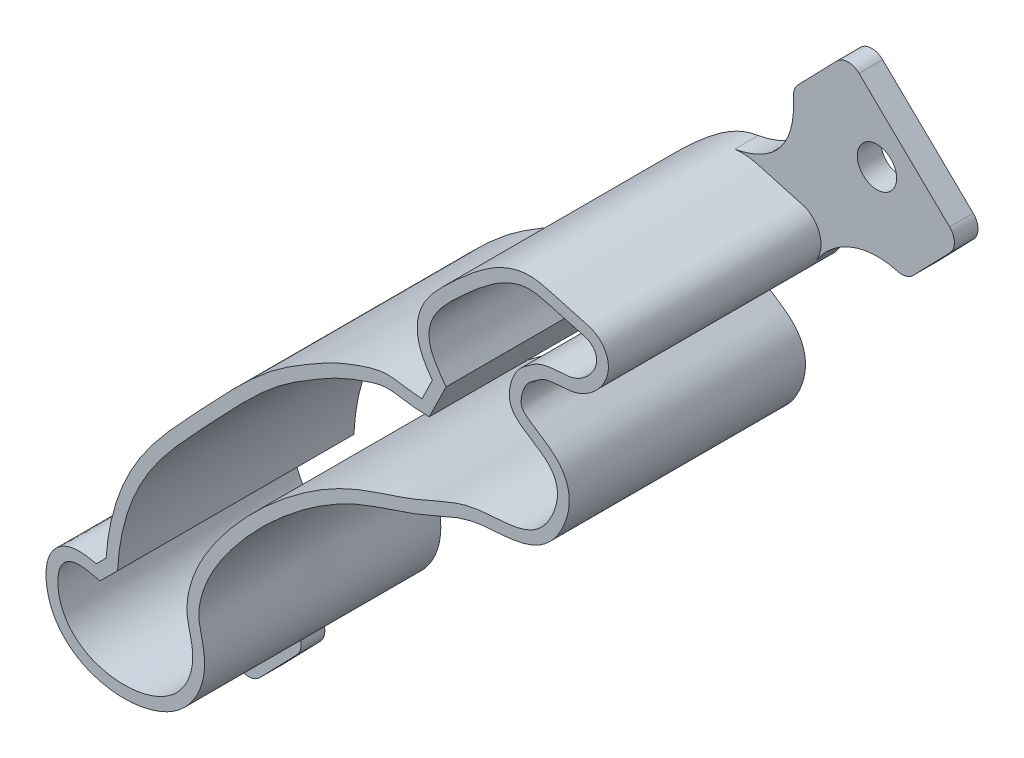
SolidWorks part; units mm, degrees
ref_plane "Ebene vorne" through (0, 0, 0) normal (0, 0, 1) x (1, 0, 0)
ref_plane "Ebene oben" through (0, 0, 0) normal (0, 1, 0) x (1, 0, 0)
ref_plane "Ebene rechts" through (0, 0, 0) normal (1, 0, 0) x (0, 0, -1)
sketch "Skizze1" plane through (0, 0, 0) normal (0, 0, 1) x (1, 0, 0)
  line L0 (3.6915, 65.7262) -> (0.7973, 62.832) construction
  line L1 (-21.9474, 134.02) -> (74.3619, 134.02)
  line L2 (-21.9474, 134.02) -> (-21.9474, 36.7449)
  line L3 (-21.9474, 36.7449) -> (74.3619, 36.7449)
  line L4 (74.3619, 134.02) -> (74.3619, 36.7449)
  line L5 (45.594, 107.3535) -> (42.9287, 101.9106) construction
  line L6 (2.714, 66.1629) -> (0.4847, 63.9336)
  line L7 (44.4296, 107.2495) -> (42.2952, 102.8907)
  line L8 (42.6847, 107.097) -> (41.3682, 104.4084)
  line L9 (1.2547, 66.825) -> (0.0178, 65.588)
  spline S0 degree 3 poles (42.9287, 101.9106) (41.9083, 101.8557) (38.2147, 102.076) (37.232, 102.6965) (31.9316, 100.9839) (28.0061, 98.7507) (22.7024, 95.5617) (14.2642, 86.5458) (7.4524, 79.4264) (4.3922, 72.3477) (3.7807, 67.4967) (3.6915, 65.7262) knots 0.063529 0.063529 0.063529 0.063529 0.070285 0.087681 0.092898 0.122457 0.165028 0.207058 0.265707 0.323851 0.34846 0.34846 0.34846 0.34846 construction
  spline S1 degree 1 poles (41.3682, 104.4084) (1.2547, 66.825) knots 0 0 1 1 construction
  spline S2 degree 1 poles (0.0178, 65.588) (42.6847, 107.097) knots 0 0 1 1 construction
  spline S3 degree 3 poles (0.7973, 62.832) (-0.6459, 63.1575) (-3.9162, 64.2409) (-4.2126, 54.5948) (8.7485, 53.658) (11.8935, 61.2324) (10.1698, 65.6836) (11.1268, 70.9286) (16.6665, 80.6) (29.3761, 91.1276) (39.603, 93.1797) (47.3265, 97.3738) (55.3614, 96.7842) (58.0777, 102.3658) (57.1454, 104.7372) (52.6747, 107.1209) (50.9529, 109.6957) (52.1672, 114.0977) (55.0363, 116.1936) (56.4019, 117.063) (61.4772, 117.182) (63.4367, 120.0126) (61.869, 120.5924) (61.7222, 120.6467) (60.162, 121.0131) (59.234, 121.3398) (53.2623, 122.9208) (45.6512, 116.4313) (41.7541, 112.3151) (44.8583, 108.3633) (45.594, 107.3535) knots 0.374666 0.374666 0.374666 0.374666 0.391641 0.407944 0.473303 0.502296 0.522992 0.546334 0.583493 0.700563 0.769326 0.809286 0.837757 0.851572 0.873854 0.890084 0.912633 0.932639 0.950409 0.980022 0.984981 1 1 1 1.001406 1.012651 1.01512 1.024688 1.038807 1.044077 1.044077 1.044077 1.044077 construction
  spline S4 degree 1 poles (0.4847, 63.9336) (44.4296, 107.2495) knots 0 0 1 1 construction
  spline S5 degree 1 poles (42.2952, 102.8907) (2.714, 66.1629) knots 0 0 1 1 construction
  spline S6 degree 3 poles (0.4847, 63.9336) (0.2533, 63.9899) (-0.2031, 64.1028) (-0.9283, 64.2622) (-1.6598, 64.3752) (-2.4053, 64.4005) (-3.1768, 64.2828) (-3.974, 63.8415) (-4.48, 63.1603) (-4.8399, 62.1917) (-4.926, 60.9133) (-4.6834, 59.3782) (-4.153, 58.0118) (-3.1124, 56.4586) (-1.3176, 55.0499) (1.2556, 54.1512) (3.9949, 53.9411) (6.6756, 54.3696) (9.0932, 55.4164) (10.9575, 57.1493) (12.0462, 59.2867) (12.3929, 61.6391) (11.9503, 63.8269) (11.4994, 65.6129) (11.5221, 67.3201) (11.9009, 69.1467) (12.5196, 70.9151) (13.5792, 73.1621) (15.3184, 75.8574) (17.8439, 79.0089) (21.6374, 82.9522) (25.8529, 86.3595) (30.056, 88.9369) (33.0477, 90.343) (35.966, 91.3595) (38.4926, 92.1781) (40.6192, 92.9605) (42.8498, 93.9105) (45.1028, 94.9874) (47.4532, 95.6259) (48.944, 95.855) (50.6074, 95.9751) (52.5048, 96.0691) (54.3995, 96.5147) (55.7737, 97.1436) (56.9742, 98.2391) (57.8011, 99.5683) (58.3464, 100.9293) (58.6088, 102.1775) (58.553, 103.3748) (57.9792, 104.8273) (56.533, 106.1381) (54.3911, 107.385) (53.0323, 108.509) (52.5721, 109.3795) (52.4407, 110.2399) (52.5026, 111.3282) (52.9569, 112.8587) (53.666, 113.8418) (54.348, 114.4424) (54.9062, 114.8487) (55.4432, 115.2245) (55.8957, 115.4971) (56.3872, 115.7154) (57.0328, 115.8995) (57.7786, 116.0187) (58.5502, 116.0887) (59.1884, 116.1215) (60.0915, 116.1629) (61.2137, 116.5113) (62.1583, 117.1633) (62.9316, 117.9806) (63.3859, 118.7822) (63.5585, 119.5362) (63.5308, 120.1761) (63.2428, 120.8291) (62.7282, 121.3205) (62.0535, 121.6062) (61.5422, 121.714) (61.1441, 121.8176) (60.6212, 121.9545) (59.971, 122.1381) (59.1595, 122.3697) (58.3317, 122.602) (57.5985, 122.8014) (56.7357, 123.0413) (55.6119, 123.2921) (54.2994, 123.2816) (53.0627, 122.966) (51.8708, 122.4503) (50.347, 121.561) (48.5516, 120.1862) (46.6451, 118.4824) (45.0102, 116.9674) (43.6659, 115.5086) (42.6769, 114.0164) (42.1669, 112.3473) (42.3566, 110.5489) (43.2754, 108.8109) (44.0453, 107.7707) (44.4296, 107.2495) knots 0.376786 0.376786 0.376786 0.376786 0.379389 0.381993 0.384596 0.387199 0.389802 0.392406 0.395009 0.397612 0.402819 0.408026 0.413232 0.418439 0.428852 0.439265 0.449679 0.460092 0.470505 0.480918 0.491332 0.501745 0.512158 0.522571 0.532985 0.543398 0.553811 0.564224 0.585051 0.605877 0.626704 0.668357 0.689183 0.71001 0.730836 0.751663 0.762076 0.772489 0.793316 0.803729 0.808936 0.814142 0.824555 0.829762 0.834969 0.840175 0.845382 0.850589 0.855795 0.861002 0.866208 0.876622 0.887035 0.897448 0.907861 0.913068 0.918275 0.928688 0.939101 0.944308 0.949514 0.954721 0.959928 0.965134 0.970341 0.975548 0.978151 0.980754 0.983357 0.985961 0.988564 0.991167 0.993771 0.995072 0.996374 0.997676 0.998977 1.000279 1.001581 1.002882 1.004184 1.006787 1.009391 1.010692 1.011994 1.013296 1.014597 1.015899 1.017201 1.018502 1.019804 1.022407 1.02501 1.027614 1.030217 1.03282 1.035424 1.038027 1.04063 1.043234 1.043234 1.043234 1.043234
  spline S7 degree 3 poles (42.2952, 102.8907) (41.989, 102.8873) (41.3655, 102.8995) (40.2078, 102.9796) (39.0884, 103.1293) (38.0973, 103.3081) (37.0856, 103.4164) (35.9396, 103.3029) (34.5685, 102.8943) (33.3088, 102.4506) (31.8555, 101.8875) (30.3531, 101.1995) (28.8995, 100.4049) (27.6162, 99.6543) (25.8861, 98.6238) (23.7019, 97.1885) (20.8737, 94.8477) (17.8729, 91.86) (13.9715, 87.7156) (10.6469, 84.2224) (7.9103, 80.8592) (6.1781, 78.2594) (4.7907, 75.5365) (3.9192, 73.1482) (3.3921, 71.1503) (3.0811, 69.613) (2.8898, 68.2541) (2.7769, 67.0967) (2.7323, 66.4705) (2.714, 66.1629) knots 0.064903 0.064903 0.064903 0.064903 0.067105 0.069306 0.073709 0.078112 0.082515 0.086918 0.091321 0.095724 0.100126 0.108932 0.117738 0.126544 0.13535 0.152961 0.170573 0.188185 0.205796 0.241019 0.258631 0.276243 0.293854 0.311466 0.320272 0.329077 0.337883 0.342286 0.346689 0.346689 0.346689 0.346689
  spline S8 degree 3 poles (41.3682, 104.4084) (41.1104, 104.4208) (40.5719, 104.4592) (39.6868, 104.5583) (38.8393, 104.6968) (37.7854, 104.8743) (36.404, 104.9033) (34.8909, 104.5784) (33.4947, 104.1086) (32.3001, 103.6749) (30.8707, 103.0945) (29.3775, 102.3852) (27.9243, 101.5724) (26.6682, 100.8379) (24.9213, 99.7889) (22.6766, 98.2986) (19.7532, 95.8536) (16.7565, 92.8617) (13.8703, 89.7975) (11.2805, 87.061) (8.9256, 84.4749) (6.8284, 81.9165) (5.0114, 79.2357) (3.5384, 76.4163) (2.5994, 73.9413) (2.0237, 71.8776) (1.6794, 70.2945) (1.4621, 68.9123) (1.3305, 67.7496) (1.2772, 67.1303) (1.2547, 66.825) knots 0.067302 0.067302 0.067302 0.067302 0.069464 0.071627 0.075951 0.080276 0.084601 0.088926 0.09325 0.097575 0.1019 0.110549 0.119199 0.127848 0.136497 0.153796 0.171095 0.188394 0.205693 0.222992 0.240291 0.257589 0.274888 0.292187 0.309486 0.318135 0.326785 0.335434 0.339759 0.344084 0.344084 0.344084 0.344084
  spline S9 degree 3 poles (0.0178, 65.588) (-0.2446, 65.6481) (-0.7552, 65.7569) (-1.6299, 65.8824) (-2.6147, 65.9025) (-3.6038, 65.7183) (-4.4698, 65.2943) (-5.2651, 64.6637) (-5.8826, 63.7484) (-6.2396, 62.6946) (-6.4245, 61.3743) (-6.3203, 59.8216) (-5.8387, 58.0647) (-5.0177, 56.5203) (-3.9281, 55.2338) (-2.65, 54.2212) (-0.7842, 53.2157) (1.7288, 52.537) (4.8083, 52.4842) (7.7736, 53.1266) (10.5042, 54.5338) (12.5598, 56.7858) (13.4802, 58.9919) (13.7797, 60.8317) (13.751, 62.7389) (13.3717, 64.2393) (13.1171, 65.3915) (13.0283, 66.036) (13.0235, 66.7211) (13.1216, 67.7047) (13.4385, 69.0348) (14.0289, 70.6273) (14.7859, 72.1632) (15.7049, 73.6861) (17.1263, 75.7273) (19.1661, 78.2347) (22.8436, 82.0121) (26.9149, 85.2683) (30.9285, 87.6989) (33.7196, 88.9912) (36.5314, 89.9657) (39.0742, 90.7913) (41.2572, 91.599) (43.0064, 92.3496) (44.6545, 93.1121) (46.3195, 93.7661) (47.837, 94.17) (49.1568, 94.3677) (50.3297, 94.4497) (51.7308, 94.5326) (53.2681, 94.7041) (54.9183, 95.0969) (56.6332, 95.8844) (58.1853, 97.3222) (59.1513, 98.9033) (59.7843, 100.4793) (60.1152, 102.0147) (60.053, 103.6667) (59.4415, 105.2251) (58.4769, 106.4166) (57.3683, 107.31) (56.3045, 108.0018) (55.0197, 108.8081) (54.347, 109.3799) (54.0943, 109.7533) (54.0082, 109.9644) (53.953, 110.2478) (53.9713, 110.7875) (54.1064, 111.4503) (54.3428, 112.0992) (54.5981, 112.5612) (54.8697, 112.892) (55.2317, 113.2263) (55.6976, 113.5715) (56.2375, 113.9499) (56.5606, 114.1467) (56.8435, 114.2784) (57.1873, 114.3861) (57.6045, 114.4706) (57.9993, 114.5287) (58.4011, 114.57) (58.7765, 114.5974) (59.0685, 114.6144) (59.4419, 114.6294) (59.9777, 114.6687) (60.6224, 114.7675) (61.3906, 114.9921) (62.1053, 115.3341) (62.9384, 115.8727) (63.8276, 116.6907) (64.5363, 117.7001) (64.9401, 118.7416) (65.0925, 119.7053) (64.9284, 120.8817) (64.2466, 122.0297) (63.2561, 122.7748) (62.202, 123.1155) (61.802, 123.1941) (61.4143, 123.2974) (61.048, 123.3942) (60.5394, 123.5358) (59.9573, 123.7023) (59.2208, 123.9106) (58.5748, 124.0909) (57.9344, 124.2653) (57.3668, 124.4197) (56.639, 124.6057) (55.7087, 124.7819) (54.5804, 124.782) (53.5195, 124.6454) (52.2808, 124.2843) (50.4837, 123.4427) (48.4871, 122.0762) (46.3975, 120.2834) (44.655, 118.6988) (43.0967, 117.1499) (41.7983, 115.5106) (40.8434, 113.5397) (40.6832, 111.5445) (41.0463, 109.9938) (41.525, 108.8941) (42.0929, 107.9456) (42.482, 107.3811) (42.6847, 107.097) knots 0.37978 0.37978 0.37978 0.37978 0.382367 0.384954 0.387541 0.390128 0.391421 0.392714 0.395301 0.397888 0.400475 0.405649 0.410823 0.415997 0.421171 0.426345 0.431518 0.441866 0.452214 0.462561 0.472909 0.483257 0.493605 0.498778 0.503952 0.5143 0.519474 0.524648 0.529821 0.534995 0.545343 0.555691 0.566038 0.576386 0.586734 0.607429 0.628125 0.669515 0.690211 0.710906 0.731602 0.752297 0.762645 0.772992 0.78334 0.793688 0.804036 0.809209 0.814383 0.819557 0.824731 0.829905 0.835079 0.840252 0.845426 0.8506 0.855774 0.860948 0.866122 0.871296 0.876469 0.881643 0.886817 0.897165 0.902339 0.907512 0.912686 0.91786 0.923034 0.928208 0.933382 0.938556 0.943729 0.948903 0.954077 0.959251 0.964425 0.969599 0.972186 0.974773 0.977359 0.978653 0.979946 0.98124 0.982533 0.983827 0.98512 0.986414 0.987707 0.990294 0.992881 0.994174 0.995468 0.996761 0.998055 0.999348 1.000642 1.001935 1.003229 1.004522 1.005816 1.008403 1.009696 1.010989 1.012283 1.01293 1.013576 1.01487 1.015517 1.016163 1.017457 1.01875 1.021337 1.023924 1.026511 1.029098 1.031685 1.034272 1.036859 1.038152 1.039446 1.040739 1.042033 1.042033 1.042033 1.042033
  dimension "D2" = 2.5
  dimension "D1" = 1
extrude "Aufsatz-Linear austragen1" add sketch "Skizze1" along normal blind 30
sketch "Skizze4" plane through (0, 0, 0) normal (0, 0, 1) x (1, 0, 0)
  line L0 (-15.025, 56.1113) -> (32.4498, 105.1573) construction
  line L1 (61.3808, 110.7847) -> (50.969, 120.863) construction
  line L2 (-0.6546, 42.2012) -> (46.8202, 91.2472) construction
  line L3 (46.8202, 91.2472) -> (32.4498, 105.1573) construction
  line L5 (-15.025, 56.1113) -> (-21.9801, 48.9261)
  line L6 (-0.6546, 42.2012) -> (-7.6096, 35.016)
  line L7 (-21.9801, 48.9261) -> (-7.6096, 35.016)
  line L8 (-14.7948, 41.971) -> (75.6207, 135.3789) construction
  line L9 (75.6207, 135.3789) -> (-14.7948, 41.971) construction
  line L10 (68.4355, 142.3339) -> (82.8059, 128.4238)
  line L11 (68.4355, 142.3339) -> (61.4804, 135.1487)
  line L12 (82.8059, 128.4238) -> (75.8509, 121.2386)
  line L14 (1.2547, 66.825) -> (0.0178, 65.588)
  line L15 (38.6417, 108.1277) -> (49.0535, 98.0494) construction
  line L16 (42.6847, 107.097) -> (41.3682, 104.4084)
  line L17 (1.2547, 66.825) -> (0.0178, 65.588)
  line L18 (42.6847, 107.097) -> (41.3682, 104.4084)
  arc A2 (64.3097, 117.4146) -> (75.8509, 121.2386) centre (72.2391, 112.8109) cw
  circle A3 centre (72.1432, 131.7863) radius 2.5
  circle A4 centre (-11.3173, 45.5636) radius 2.5
  spline S0 degree 2 poles (-0.6546, 42.2012) (-4.002, 50.1099) (5.5816, 52.7021) knots 0 0 0 1 1 1
  spline S1 degree 3 poles (0.0178, 65.588) (-0.2446, 65.6481) (-0.7552, 65.7569) (-1.6299, 65.8824) (-2.6147, 65.9025) (-3.6038, 65.7183) (-4.4698, 65.2943) (-5.2651, 64.6637) (-5.8826, 63.7484) (-6.2396, 62.6946) (-6.4245, 61.3743) (-6.3203, 59.8216) (-5.8387, 58.0647) (-5.0177, 56.5203) (-3.9281, 55.2338) (-2.65, 54.2212) (-0.7842, 53.2157) (1.7288, 52.537) (4.8083, 52.4842) (7.7736, 53.1266) (10.5042, 54.5338) (12.5598, 56.7858) (13.4802, 58.9919) (13.7797, 60.8317) (13.751, 62.7389) (13.3717, 64.2393) (13.1171, 65.3915) (13.0283, 66.036) (13.0235, 66.7211) (13.1216, 67.7047) (13.4385, 69.0348) (14.0289, 70.6273) (14.7859, 72.1632) (15.7049, 73.6861) (17.1263, 75.7273) (19.1661, 78.2347) (22.8436, 82.0121) (26.9149, 85.2683) (30.9285, 87.6989) (33.7196, 88.9912) (36.5314, 89.9657) (39.0742, 90.7913) (41.2572, 91.599) (43.0064, 92.3496) (44.6545, 93.1121) (46.3195, 93.7661) (47.837, 94.17) (49.1568, 94.3677) (50.3297, 94.4497) (51.7308, 94.5326) (53.2681, 94.7041) (54.9183, 95.0969) (56.6332, 95.8844) (58.1853, 97.3222) (59.1513, 98.9033) (59.7843, 100.4793) (60.1152, 102.0147) (60.053, 103.6667) (59.4415, 105.2251) (58.4769, 106.4166) (57.3683, 107.31) (56.3045, 108.0018) (55.0197, 108.8081) (54.347, 109.3799) (54.0943, 109.7533) (54.0082, 109.9644) (53.953, 110.2478) (53.9713, 110.7875) (54.1064, 111.4503) (54.3428, 112.0992) (54.5981, 112.5612) (54.8697, 112.892) (55.2317, 113.2263) (55.6976, 113.5715) (56.2375, 113.9499) (56.5606, 114.1467) (56.8435, 114.2784) (57.1873, 114.3861) (57.6045, 114.4706) (57.9993, 114.5287) (58.4011, 114.57) (58.7765, 114.5974) (59.0685, 114.6144) (59.4419, 114.6294) (59.9777, 114.6687) (60.6224, 114.7675) (61.3906, 114.9921) (62.1053, 115.3341) (62.9384, 115.8727) (63.8276, 116.6907) (64.5363, 117.7001) (64.9401, 118.7416) (65.0925, 119.7053) (64.9284, 120.8817) (64.2466, 122.0297) (63.2561, 122.7748) (62.202, 123.1155) (61.802, 123.1941) (61.4143, 123.2974) (61.048, 123.3942) (60.5394, 123.5358) (59.9573, 123.7023) (59.2208, 123.9106) (58.5748, 124.0909) (57.9344, 124.2653) (57.3668, 124.4197) (56.639, 124.6057) (55.7087, 124.7819) (54.5804, 124.782) (53.5195, 124.6454) (52.2808, 124.2843) (50.4837, 123.4427) (48.4871, 122.0762) (46.3975, 120.2834) (44.655, 118.6988) (43.0967, 117.1499) (41.7983, 115.5106) (40.8434, 113.5397) (40.6832, 111.5445) (41.0463, 109.9938) (41.525, 108.8941) (42.0929, 107.9456) (42.482, 107.3811) (42.6847, 107.097) knots 0.37978 0.37978 0.37978 0.37978 0.382367 0.384954 0.387541 0.390128 0.391421 0.392714 0.395301 0.397888 0.400475 0.405649 0.410823 0.415997 0.421171 0.426345 0.431518 0.441866 0.452214 0.462561 0.472909 0.483257 0.493605 0.498778 0.503952 0.5143 0.519474 0.524648 0.529821 0.534995 0.545343 0.555691 0.566038 0.576386 0.586734 0.607429 0.628125 0.669515 0.690211 0.710906 0.731602 0.752297 0.762645 0.772992 0.78334 0.793688 0.804036 0.809209 0.814383 0.819557 0.824731 0.829905 0.835079 0.840252 0.845426 0.8506 0.855774 0.860948 0.866122 0.871296 0.876469 0.881643 0.886817 0.897165 0.902339 0.907512 0.912686 0.91786 0.923034 0.928208 0.933382 0.938556 0.943729 0.948903 0.954077 0.959251 0.964425 0.969599 0.972186 0.974773 0.977359 0.978653 0.979946 0.98124 0.982533 0.983827 0.98512 0.986414 0.987707 0.990294 0.992881 0.994174 0.995468 0.996761 0.998055 0.999348 1.000642 1.001935 1.003229 1.004522 1.005816 1.008403 1.009696 1.010989 1.012283 1.01293 1.013576 1.01487 1.015517 1.016163 1.017457 1.01875 1.021337 1.023924 1.026511 1.029098 1.031685 1.034272 1.036859 1.038152 1.039446 1.040739 1.042033 1.042033 1.042033 1.042033 construction
  spline S2 degree 2 poles (-15.025, 56.1113) (-8.2671, 52.5844) (-6.3659, 60.7912) knots 0 0 0 1 1 1
  spline S3 degree 2 poles (61.4804, 135.1487) (62.4216, 126.0481) (53.5986, 124.6297) knots 0 0 0 1 1 1
  spline S6 degree 3 poles (4998.5455, 134.1377) (-31.3, 38.3448) (16.0887, 63.3399) (-1.6299, 65.8824) (-2.6147, 65.9025) (-3.6038, 65.7183) (-4.4698, 65.2943) (-5.2651, 64.6637) (-5.8826, 63.7484) (-6.2396, 62.6946) (-6.4245, 61.3743) (-6.3203, 59.8216) (-5.8387, 58.0647) (-5.0177, 56.5203) (-3.9281, 55.2338) (-2.65, 54.2212) (-0.7842, 53.2157) (1.7288, 52.537) (4.8083, 52.4842) (7.7736, 53.1266) (10.5042, 54.5338) (12.5598, 56.7858) (13.4802, 58.9919) (13.7797, 60.8317) (13.751, 62.7389) (13.3717, 64.2393) (13.1171, 65.3915) (13.0283, 66.036) (13.0235, 66.7211) (13.1216, 67.7047) (13.4385, 69.0348) (14.0289, 70.6273) (14.7859, 72.1632) (15.7049, 73.6861) (17.1263, 75.7273) (19.1661, 78.2347) (22.8436, 82.0121) (26.9149, 85.2683) (30.9285, 87.6989) (33.7196, 88.9912) (36.5314, 89.9657) (39.0742, 90.7913) (41.2572, 91.599) (43.0064, 92.3496) (44.6545, 93.1121) (46.3195, 93.7661) (47.837, 94.17) (49.1568, 94.3677) (50.3297, 94.4497) (51.7308, 94.5326) (53.2681, 94.7041) (54.9183, 95.0969) (56.6332, 95.8844) (58.1853, 97.3222) (59.1513, 98.9033) (59.7843, 100.4793) (60.1152, 102.0147) (60.053, 103.6667) (59.4415, 105.2251) (58.4769, 106.4166) (57.3683, 107.31) (56.3045, 108.0018) (55.0197, 108.8081) (54.347, 109.3799) (54.0943, 109.7533) (54.0082, 109.9644) (53.953, 110.2478) (53.9713, 110.7875) (54.1064, 111.4503) (54.3428, 112.0992) (54.5981, 112.5612) (54.8697, 112.892) (55.2317, 113.2263) (55.6976, 113.5715) (56.2375, 113.9499) (56.5606, 114.1467) (56.8435, 114.2784) (57.1873, 114.3861) (57.6045, 114.4706) (57.9993, 114.5287) (58.4011, 114.57) (58.7765, 114.5974) (59.0685, 114.6144) (59.4419, 114.6294) (59.9777, 114.6687) (60.6224, 114.7675) (61.3906, 114.9921) (62.1053, 115.3341) (62.9384, 115.8727) (63.8276, 116.6907) (64.5363, 117.7001) (64.9401, 118.7416) (65.0925, 119.7053) (64.9284, 120.8817) (64.2466, 122.0297) (63.2561, 122.7748) (62.202, 123.1155) (61.802, 123.1941) (61.4143, 123.2974) (61.048, 123.3942) (60.5394, 123.5358) (59.9573, 123.7023) (59.2208, 123.9106) (58.5748, 124.0909) (57.9344, 124.2653) (57.3668, 124.4197) (56.639, 124.6057) (55.7087, 124.7819) (54.5804, 124.782) (53.5195, 124.6454) (52.2808, 124.2843) (50.4837, 123.4427) (48.4871, 122.0762) (46.3975, 120.2834) (44.655, 118.6988) (43.0967, 117.1499) (41.7983, 115.5106) (40.8434, 113.5397) (40.6832, 111.5445) (41.0463, 109.9938) (41.525, 108.8941) (53.9958, 88.0622) (77.418, 139.0224) (1547.2827, -4659.1555) knots 0.230327 0.230327 0.230327 0.230327 0.382367 0.384954 0.387541 0.390128 0.391421 0.392714 0.395301 0.397888 0.400475 0.405649 0.410823 0.415997 0.421171 0.426345 0.431518 0.441866 0.452214 0.462561 0.472909 0.483257 0.493605 0.498778 0.503952 0.5143 0.519474 0.524648 0.529821 0.534995 0.545343 0.555691 0.566038 0.576386 0.586734 0.607429 0.628125 0.669515 0.690211 0.710906 0.731602 0.752297 0.762645 0.772992 0.78334 0.793688 0.804036 0.809209 0.814383 0.819557 0.824731 0.829905 0.835079 0.840252 0.845426 0.8506 0.855774 0.860948 0.866122 0.871296 0.876469 0.881643 0.886817 0.897165 0.902339 0.907512 0.912686 0.91786 0.923034 0.928208 0.933382 0.938556 0.943729 0.948903 0.954077 0.959251 0.964425 0.969599 0.972186 0.974773 0.977359 0.978653 0.979946 0.98124 0.982533 0.983827 0.98512 0.986414 0.987707 0.990294 0.992881 0.994174 0.995468 0.996761 0.998055 0.999348 1.000642 1.001935 1.003229 1.004522 1.005816 1.008403 1.009696 1.010989 1.012283 1.01293 1.013576 1.01487 1.015517 1.016163 1.017457 1.01875 1.021337 1.023924 1.026511 1.029098 1.031685 1.034272 1.036859 1.038152 1.039446 1.040739 1.123373 1.123373 1.123373 1.123373 only from (0.0178, 65.588) to (42.6847, 107.097)
  spline S7 degree 3 poles (-4919.3554, 725.3748) (133.1044, 109.8366) (52.0134, 103.1792) (39.6868, 104.5583) (38.8393, 104.6968) (37.7854, 104.8743) (36.404, 104.9033) (34.8909, 104.5784) (33.4947, 104.1086) (32.3001, 103.6749) (30.8707, 103.0945) (29.3775, 102.3852) (27.9243, 101.5724) (26.6682, 100.8379) (24.9213, 99.7889) (22.6766, 98.2986) (19.7532, 95.8536) (16.7565, 92.8617) (13.8703, 89.7975) (11.2805, 87.061) (8.9256, 84.4749) (6.8284, 81.9165) (5.0114, 79.2357) (3.5384, 76.4163) (2.5994, 73.9413) (2.0237, 71.8776) (1.6794, 70.2945) (1.4621, 68.9123) (-1.0128, 47.0517) (13.3797, -25.1525) (418.9565, 5048.9465) knots -0.044505 -0.044505 -0.044505 -0.044505 0.069464 0.071627 0.075951 0.080276 0.084601 0.088926 0.09325 0.097575 0.1019 0.110549 0.119199 0.127848 0.136497 0.153796 0.171095 0.188394 0.205693 0.222992 0.240291 0.257589 0.274888 0.292187 0.309486 0.318135 0.326785 0.335434 0.339759 0.652055 0.652055 0.652055 0.652055 only from (41.3682, 104.4084) to (1.2547, 66.825)
  spline S8 degree 3 poles (0.0178, 65.588) (-0.2446, 65.6481) (-0.7552, 65.7569) (-1.6299, 65.8824) (-2.6147, 65.9025) (-3.6038, 65.7183) (-4.4698, 65.2943) (-5.2651, 64.6637) (-5.8826, 63.7484) (-6.2396, 62.6946) (-6.4245, 61.3743) (-6.3203, 59.8216) (-5.8387, 58.0647) (-5.0177, 56.5203) (-3.9281, 55.2338) (-2.65, 54.2212) (-0.7842, 53.2157) (1.7288, 52.537) (4.8083, 52.4842) (7.7736, 53.1266) (10.5042, 54.5338) (12.5598, 56.7858) (13.4802, 58.9919) (13.7797, 60.8317) (13.751, 62.7389) (13.3717, 64.2393) (13.1171, 65.3915) (13.0283, 66.036) (13.0235, 66.7211) (13.1216, 67.7047) (13.4385, 69.0348) (14.0289, 70.6273) (14.7859, 72.1632) (15.7049, 73.6861) (17.1263, 75.7273) (19.1661, 78.2347) (22.8436, 82.0121) (26.9149, 85.2683) (30.9285, 87.6989) (33.7196, 88.9912) (36.5314, 89.9657) (39.0742, 90.7913) (41.2572, 91.599) (43.0064, 92.3496) (44.6545, 93.1121) (46.3195, 93.7661) (47.837, 94.17) (49.1568, 94.3677) (50.3297, 94.4497) (51.7308, 94.5326) (53.2681, 94.7041) (54.9183, 95.0969) (56.6332, 95.8844) (58.1853, 97.3222) (59.1513, 98.9033) (59.7843, 100.4793) (60.1152, 102.0147) (60.053, 103.6667) (59.4415, 105.2251) (58.4769, 106.4166) (57.3683, 107.31) (56.3045, 108.0018) (55.0197, 108.8081) (54.347, 109.3799) (54.0943, 109.7533) (54.0082, 109.9644) (53.953, 110.2478) (53.9713, 110.7875) (54.1064, 111.4503) (54.3428, 112.0992) (54.5981, 112.5612) (54.8697, 112.892) (55.2317, 113.2263) (55.6976, 113.5715) (56.2375, 113.9499) (56.5606, 114.1467) (56.8435, 114.2784) (57.1873, 114.3861) (57.6045, 114.4706) (57.9993, 114.5287) (58.4011, 114.57) (58.7765, 114.5974) (59.0685, 114.6144) (59.4419, 114.6294) (59.9777, 114.6687) (60.6224, 114.7675) (61.3906, 114.9921) (62.1053, 115.3341) (62.9384, 115.8727) (63.8276, 116.6907) (64.5363, 117.7001) (64.9401, 118.7416) (65.0925, 119.7053) (64.9284, 120.8817) (64.2466, 122.0297) (63.2561, 122.7748) (62.202, 123.1155) (61.802, 123.1941) (61.4143, 123.2974) (61.048, 123.3942) (60.5394, 123.5358) (59.9573, 123.7023) (59.2208, 123.9106) (58.5748, 124.0909) (57.9344, 124.2653) (57.3668, 124.4197) (56.639, 124.6057) (55.7087, 124.7819) (54.5804, 124.782) (53.5195, 124.6454) (52.2808, 124.2843) (50.4837, 123.4427) (48.4871, 122.0762) (46.3975, 120.2834) (44.655, 118.6988) (43.0967, 117.1499) (41.7983, 115.5106) (40.8434, 113.5397) (40.6832, 111.5445) (41.0463, 109.9938) (41.525, 108.8941) (42.0929, 107.9456) (42.482, 107.3811) (42.6847, 107.097) knots 0.37978 0.37978 0.37978 0.37978 0.382367 0.384954 0.387541 0.390128 0.391421 0.392714 0.395301 0.397888 0.400475 0.405649 0.410823 0.415997 0.421171 0.426345 0.431518 0.441866 0.452214 0.462561 0.472909 0.483257 0.493605 0.498778 0.503952 0.5143 0.519474 0.524648 0.529821 0.534995 0.545343 0.555691 0.566038 0.576386 0.586734 0.607429 0.628125 0.669515 0.690211 0.710906 0.731602 0.752297 0.762645 0.772992 0.78334 0.793688 0.804036 0.809209 0.814383 0.819557 0.824731 0.829905 0.835079 0.840252 0.845426 0.8506 0.855774 0.860948 0.866122 0.871296 0.876469 0.881643 0.886817 0.897165 0.902339 0.907512 0.912686 0.91786 0.923034 0.928208 0.933382 0.938556 0.943729 0.948903 0.954077 0.959251 0.964425 0.969599 0.972186 0.974773 0.977359 0.978653 0.979946 0.98124 0.982533 0.983827 0.98512 0.986414 0.987707 0.990294 0.992881 0.994174 0.995468 0.996761 0.998055 0.999348 1.000642 1.001935 1.003229 1.004522 1.005816 1.008403 1.009696 1.010989 1.012283 1.01293 1.013576 1.01487 1.015517 1.016163 1.017457 1.01875 1.021337 1.023924 1.026511 1.029098 1.031685 1.034272 1.036859 1.038152 1.039446 1.040739 1.042033 1.042033 1.042033 1.042033
  spline S9 degree 3 poles (41.3682, 104.4084) (41.1104, 104.4208) (40.5719, 104.4592) (39.6868, 104.5583) (38.8393, 104.6968) (37.7854, 104.8743) (36.404, 104.9033) (34.8909, 104.5784) (33.4947, 104.1086) (32.3001, 103.6749) (30.8707, 103.0945) (29.3775, 102.3852) (27.9243, 101.5724) (26.6682, 100.8379) (24.9213, 99.7889) (22.6766, 98.2986) (19.7532, 95.8536) (16.7565, 92.8617) (13.8703, 89.7975) (11.2805, 87.061) (8.9256, 84.4749) (6.8284, 81.9165) (5.0114, 79.2357) (3.5384, 76.4163) (2.5994, 73.9413) (2.0237, 71.8776) (1.6794, 70.2945) (1.4621, 68.9123) (1.3305, 67.7496) (1.2772, 67.1303) (1.2547, 66.825) knots 0.067302 0.067302 0.067302 0.067302 0.069464 0.071627 0.075951 0.080276 0.084601 0.088926 0.09325 0.097575 0.1019 0.110549 0.119199 0.127848 0.136497 0.153796 0.171095 0.188394 0.205693 0.222992 0.240291 0.257589 0.274888 0.292187 0.309486 0.318135 0.326785 0.335434 0.339759 0.344084 0.344084 0.344084 0.344084
  dimension "D2" = 5
  dimension "D8" = 5
  dimension "D9" = 10
  dimension "D10" = 10
  dimension "D1" = 130
  dimension "D3" = 20
  dimension "D4" = 20
  dimension "D5" = 10
  dimension "D6" = 10
  dimension "D7" = 10
  dimension "D11" = 0
extrude "Aufsatz-Linear austragen2" add sketch "Skizze4" along normal blind 3
fillet "Verrundung2" radius 2 8 edges at (75.8509, 121.2386, 1.5) (82.8059, 128.4238, 1.5) (68.4355, 142.3339, 1.5) (-21.9801, 48.9261, 1.5) (-7.6096, 35.016, 1.5) (-0.6546, 42.2012, 1.5) (-15.025, 56.1113, 1.5) (61.4804, 135.1487, 1.5)
